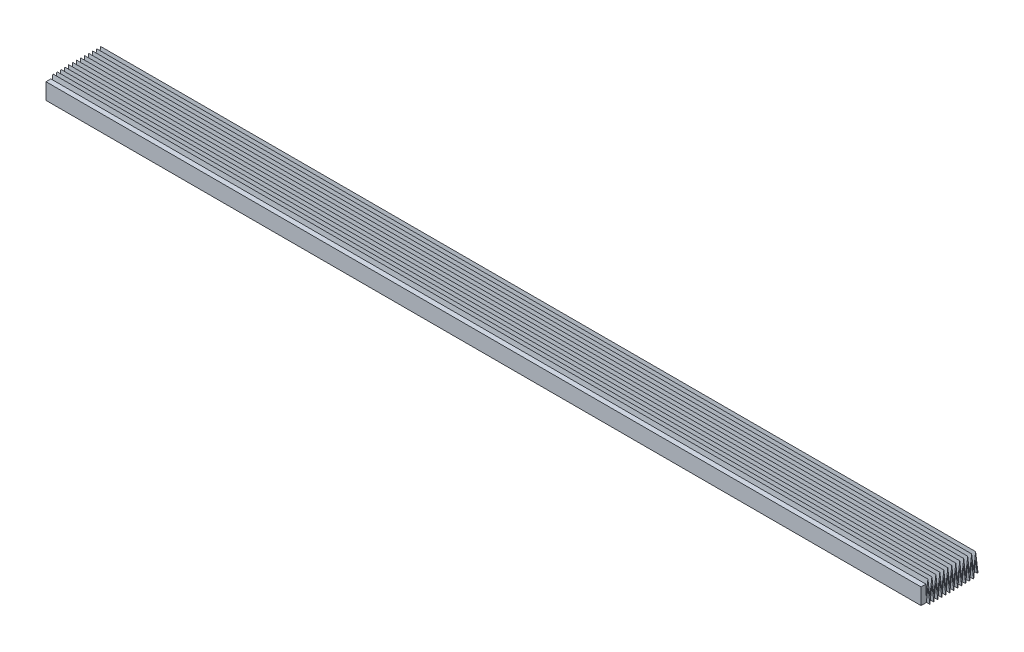
SolidWorks part; units mm, degrees
ref_plane "Front Plane" through (0, 0, 0) normal (0, 0, 1) x (1, 0, 0)
ref_plane "Top Plane" through (0, 0, 0) normal (0, 1, 0) x (1, 0, 0)
ref_plane "Right Plane" through (0, 0, 0) normal (1, 0, 0) x (0, 0, -1)
sketch "Sketch2" plane through (0, 0, 0) normal (0, 0, 1) x (1, 0, 0)
  line L1 (-270, 10) -> (270, 10)
  line L2 (-270, 10) -> (-270, 0)
  line L3 (-270, 0) -> (270, 0)
  line L4 (270, 10) -> (270, 0)
  point P4 (0, 0)
  dimension "D1" = 10
  dimension "D2" = 540
extrude "Boss-Extrude1" add sketch "Sketch2" along normal blind 3
sketch "Sketch3" plane through (270, 0, 0) normal (1, 0, 0) x (0, 0, -1)
  line L0 (0, 10) -> (31.8884, 10) construction
  line L1 (0, 0) -> (31.8884, 0) construction
  line L3 (0, 0) -> (1.2265, 10)
  line L4 (1.2265, 10) -> (2.453, 0)
  line L5 (2.453, 0) -> (3.6794, 10)
  line L6 (3.6794, 10) -> (4.9059, 0)
  line L7 (4.9059, 0) -> (6.1324, 10)
  line L8 (6.1324, 10) -> (7.3589, 0)
  line L9 (7.3589, 0) -> (8.5853, 10)
  line L10 (8.5853, 10) -> (9.8118, 0)
  line L11 (9.8118, 0) -> (11.0383, 10)
  line L12 (11.0383, 10) -> (12.2648, 0)
  line L13 (12.2648, 0) -> (13.4912, 10)
  line L14 (13.4912, 10) -> (14.7177, 0)
  line L15 (14.7177, 0) -> (15.9442, 10)
  line L16 (15.9442, 10) -> (17.1707, 0)
  line L17 (17.1707, 0) -> (18.3972, 10)
  line L18 (18.3972, 10) -> (19.6236, 0)
  line L20 (19.6236, 0) -> (20.8501, 10)
  line L21 (20.8501, 10) -> (22.0766, 0)
  line L22 (22.0766, 0) -> (23.3031, 10)
  line L23 (23.3031, 10) -> (24.5295, 0)
  line L24 (24.5295, 0) -> (25.756, 10)
  line L25 (25.756, 10) -> (26.9825, 0)
  line L26 (26.9825, 0) -> (28.209, 10)
  line L27 (28.209, 10) -> (29.4354, 0)
  line L28 (29.4354, 0) -> (30.6619, 10)
  line L29 (30.6619, 10) -> (31.8884, 0)
  line L30 (31.8884, 10) -> (31.8884, 0) construction
  line L32 (31.8884, 10) -> (31.8884, 0) construction
extrude "Extrude-Thin1" add sketch "Sketch3" against normal through all thin thin type mid plane wall 0.5
